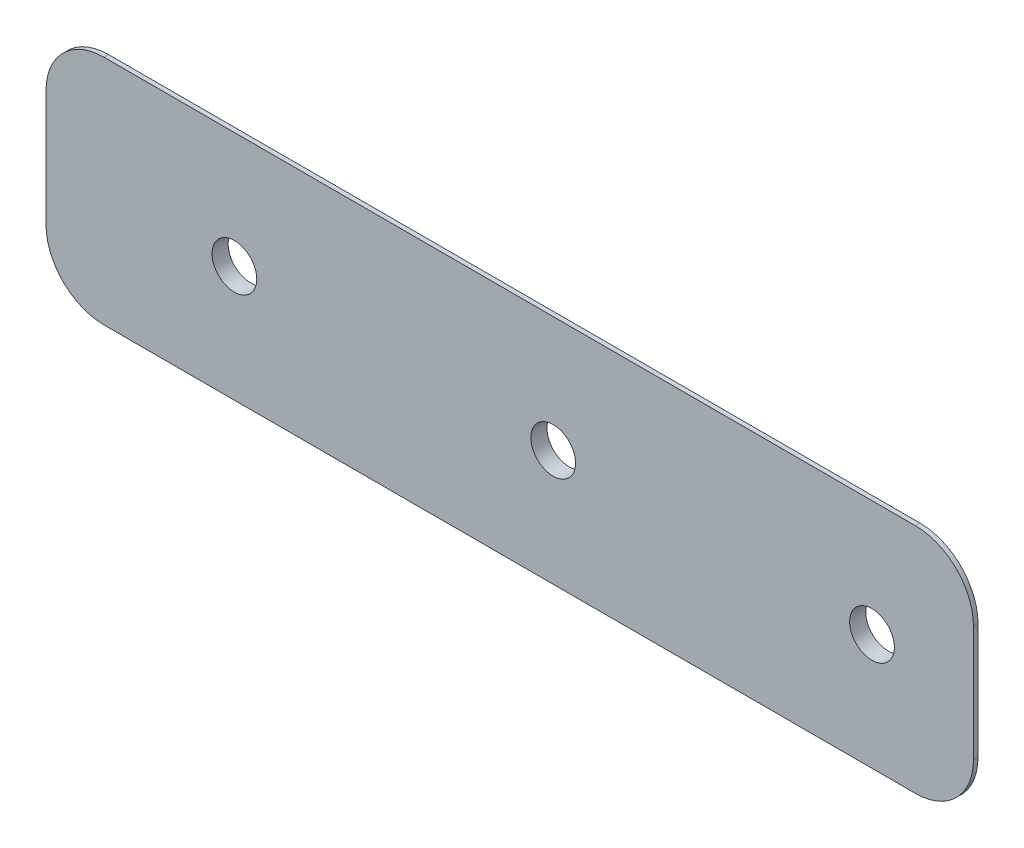
SolidWorks part; units mm, degrees
ref_plane "Front Plane" through (0, 0, 0) normal (0, 0, 1) x (1, 0, 0)
ref_plane "Top Plane" through (0, 0, 0) normal (0, 1, 0) x (1, 0, 0)
ref_plane "Right Plane" through (0, 0, 0) normal (1, 0, 0) x (0, 0, -1)
sketch "Sketch1" plane through (0, 0, 0) normal (0, 0, 1) x (1, 0, 0)
  line L0 (-69.85, 0) -> (69.85, 0) construction
  line L1 (92.075, -27.94) -> (-121.6025, -27.94) construction
  line L2 (92.075, -27.94) -> (92.075, 8.89) construction
  line L4 (-111.125, 25.4) -> (92.075, 25.4)
  line L5 (-111.125, 25.4) -> (-111.125, -25.4)
  line L6 (-111.125, -25.4) -> (92.075, -25.4)
  line L7 (92.075, 25.4) -> (92.075, -25.4)
  line L8 (-111.125, 25.4) -> (92.075, -25.4) construction
  line L9 (-111.125, -25.4) -> (92.075, 25.4) construction
  circle A0 centre (-69.85, 0) radius 6.477
  circle A1 centre (0, 0) radius 6.477
  circle A2 centre (69.85, 0) radius 6.477
  arc A3 (92.075, 8.89) -> (-78.9212, 13.8765) centre (0, -214.1523) ccw construction
  arc A4 (-78.9212, 13.8765) -> (-121.6025, -27.94) centre (-56.0756, -52.1319) ccw construction
  point P4 (0, 0)
  point P9 (-9.525, 0)
  dimension "D2" = 12.954
  dimension "D5" = 69.85
  dimension "D6" = 241.3
  dimension "D1" = 69.85
  dimension "D3" = 22.225
  dimension "D4" = 27.94
  dimension "D7" = 213.6775
  dimension "D8" = 36.83
  dimension "D9" = 50.8
  dimension "D10" = 203.2
  dimension "D11" = 22.225
extrude "Boss-Extrude1" add sketch "Sketch1" along normal blind 1 contours A0 | A1 L0 | L0 A1 | A3 A4 L1 L2 A0 A1 A2 | A2 region at (-9.9044, 0, 0) region at (-69.85, 0, 0) region at (0, 0, 0) region at (69.85, 0, 0)
extrude "Boss-Extrude2" add sketch "Sketch1<3>" against normal blind 2.54 contours A0 | A1 | A2
sketch "Sketch1<3>" plane through (0, 0, 0) normal (0, 0, 1) x (1, 0, 0) same geometry as "Sketch1"
hole_wizard "3/8 Clearance Hole1" positions "3DSketch1" profile "Sketch2" hole size "3/8" standard "ANSI Inch" end condition through all
sketch3d "3DSketch1"
  point P0 (-69.85, 0, 0)
  point P3 (0, 0, 0)
  point P6 (69.85, 0, 1)
  point P8 (0, 0, 1)
  point P10 (-69.85, 0, 1)
sketch "Sketch2" plane through (-69.85, 0, 1) normal (1, 0, 0) x (0, -1, 0)
  line L0 (0, 0) -> (0, 3.54)
  line L1 (0, 3.54) -> (4.9022, 3.54)
  line L2 (4.9022, 3.54) -> (4.9022, 0)
  line L5 (4.9022, 0) -> (0, 0)
  line L11 (0, -6.35) -> (0, 107.95) construction
  dimension "Thru Hole Dia." = 9.8044
  dimension "Thru Hole Depth" = 3.54
fillet "Fillet1" radius 12.7 4 edges at (-111.125, -25.4, 0.5) (-111.125, 25.4, 0.5) (92.075, -25.4, 0.5) (92.075, 25.4, 0.5)
